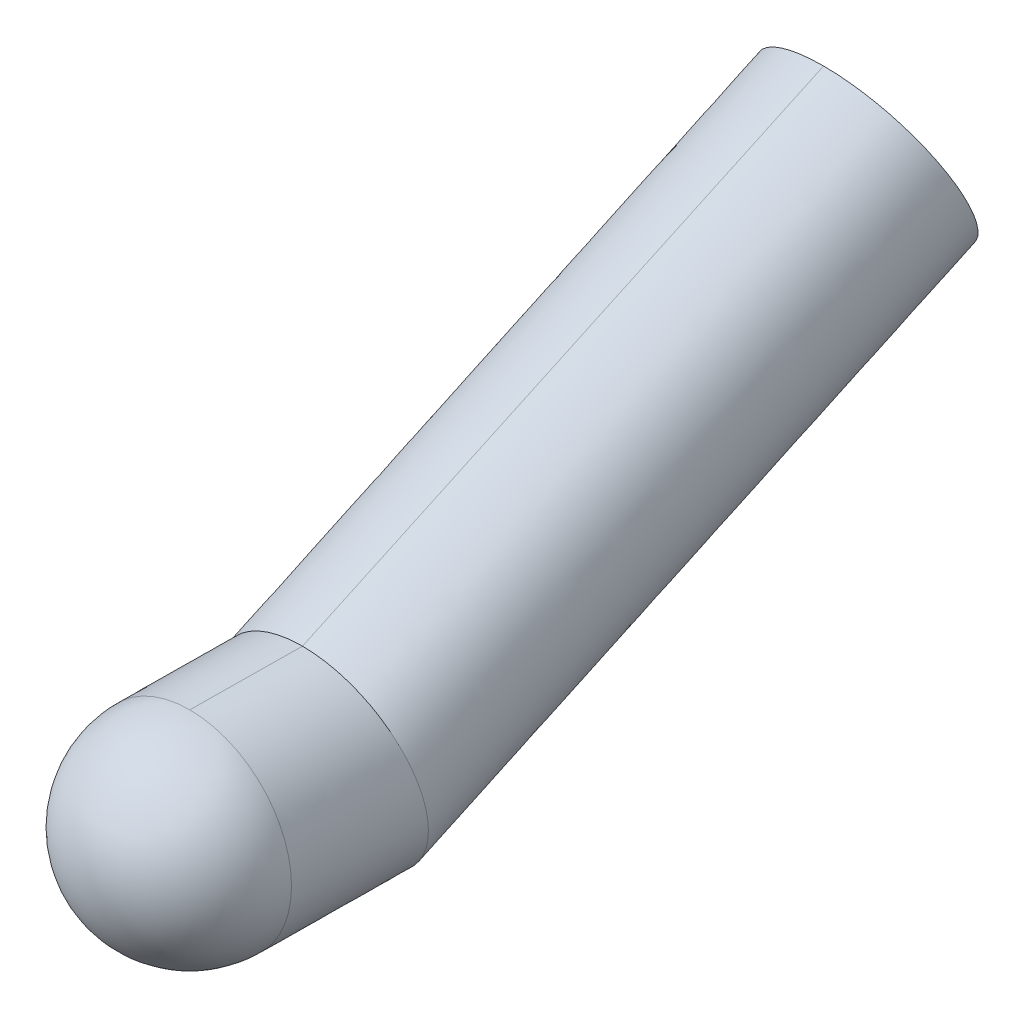
SolidWorks part; units mm, degrees
ref_plane "前视基准面" through (0, 0, 0) normal (0, 0, 1) x (1, 0, 0)
ref_plane "上视基准面" through (0, 0, 0) normal (0, 1, 0) x (1, 0, 0)
ref_plane "右视基准面" through (0, 0, 0) normal (1, 0, 0) x (0, 0, -1)
other "Configuration Table"
sketch "Sketch1" plane through (0, 0, 0) normal (0, 0, 1) x (1, 0, 0)
  line L0 (0, 5) -> (0, -5)
  line L1 (55, 0) -> (-55, 0) construction
  arc A0 (0, -5) -> (0, 5) centre (0, 0) ccw
  dimension "D1" = 10
revolve "Revolve1" add sketch "Sketch1" angle 360 about L0
extrude "Cut-Extrude1" cut sketch "Sketch1<2>" against normal blind 30
sketch "Sketch1<2>" plane through (0, 0, 0) normal (0, 0, 1) x (1, 0, 0) same geometry as "Sketch1"
sketch "Sketch3" plane through (0, 0, 0) normal (1, 0, 0) x (0, 0, -1)
  line L0 (0, 0) -> (6.618, -0.0708)
  line L1 (0, 5) -> (0, -5)
  line L2 (0, 5) -> (0, -5)
  line L3 (0, -5) -> (0, 5) construction
  line L4 (0, -5) -> (0, 5)
  line L5 (6.618, -0.0708) -> (33.3168, 12.3214)
  line L6 (0, -5) -> (0, 5)
  arc A1 (0, -5) -> (0, 5) centre (0, 0) ccw
  arc A2 (0, -5) -> (0, 5) centre (0, 0) ccw
  point P6 (9.0105, 3.549)
  point P7 (33.3168, 12.3214)
  dimension "D1" = 0
sketch "Sketch4" plane through (0, 0, 0) normal (0, 0, 1) x (1, 0, 0)
  arc A0 (0, 5) -> (0, -5) centre (0, 0) ccw construction
  arc A1 (0, 5) -> (0, -5) centre (0, 0) ccw
  arc A2 (0, -5) -> (0, 5) centre (0, 0) ccw construction
  arc A3 (0, -5) -> (0, 5) centre (0, 0) ccw
sweep "Sweep1" add profiles "Sketch4" path "Sketch3"
